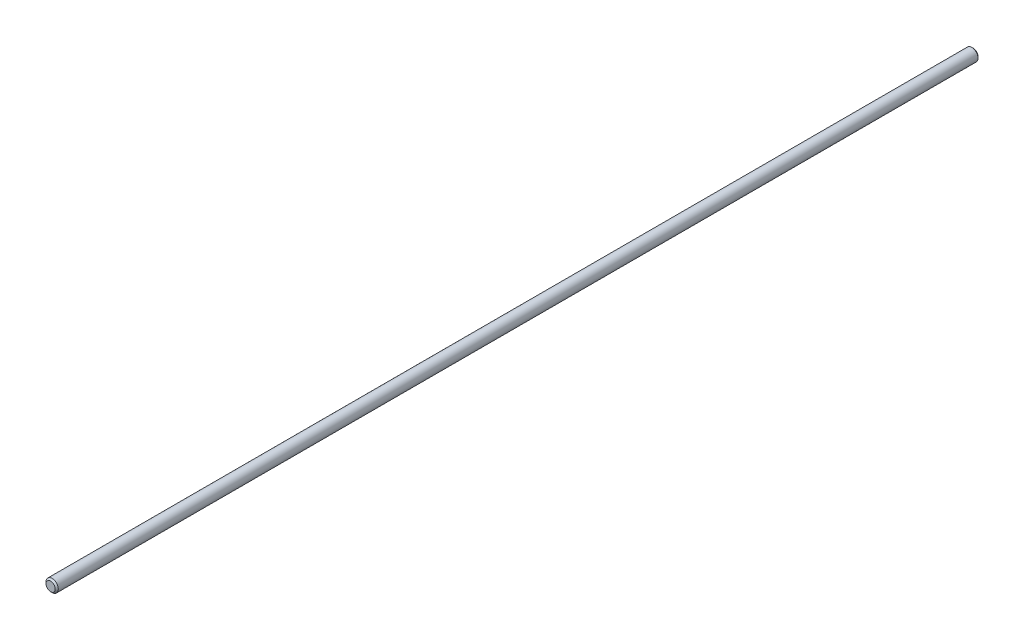
SolidWorks part; units mm, degrees
ref_plane "Front Plane" through (0, 0, 0) normal (0, 0, 1) x (1, 0, 0)
ref_plane "Top Plane" through (0, 0, 0) normal (0, 1, 0) x (1, 0, 0)
ref_plane "Right Plane" through (0, 0, 0) normal (1, 0, 0) x (0, 0, -1)
sketch "Sketch1" plane through (0, 0, 0) normal (0, 0, 1) x (1, 0, 0)
  circle A0 centre (0, 0) radius 4
  dimension "D1" = 8
extrude "Boss-Extrude1" add sketch "Sketch1" along normal blind 601
chamfer "Chamfer1" distance 1 angle 45 2 edges at (4, 0, 601) (4, 0, 0)
